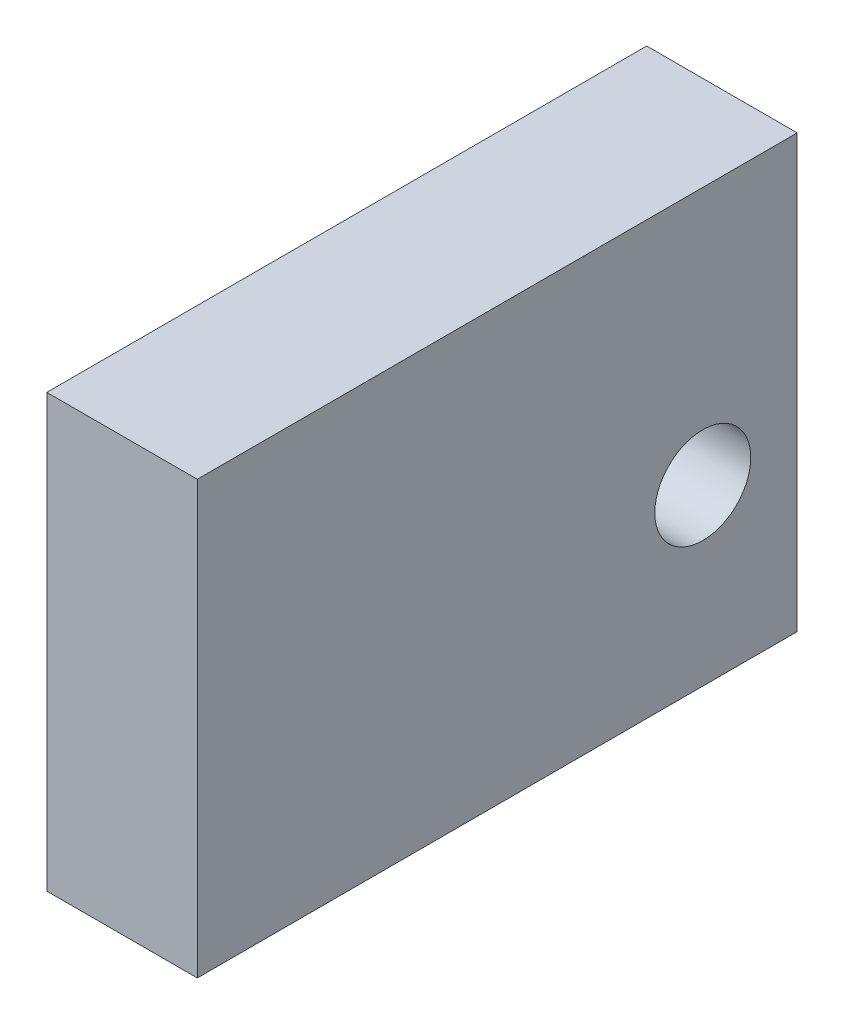
SolidWorks part; units mm, degrees
ref_plane "Front Plane" through (0, 0, 0) normal (0, 0, 1) x (1, 0, 0)
ref_plane "Top Plane" through (0, 0, 0) normal (0, 1, 0) x (1, 0, 0)
ref_plane "Right Plane" through (0, 0, 0) normal (1, 0, 0) x (0, 0, -1)
sketch "Sketch1" plane through (0, 0, 0) normal (0, 1, 0) x (1, 0, 0)
  line L1 (-1.381, 31.8279) -> (14.548, 31.8279)
  line L2 (-1.381, 31.8279) -> (-1.381, -31.6721)
  line L3 (-1.381, -31.6721) -> (14.548, -31.6721)
  line L4 (14.548, 31.8279) -> (14.548, -31.6721)
  line L5 (-1.381, 31.8279) -> (14.548, -31.6721) construction
  line L6 (-1.381, -31.6721) -> (14.548, 31.8279) construction
  point P4 (6.5835, 0.0779)
  dimension "D1" = 63.5
  dimension "D2" = 15.929
extrude "Boss-Extrude1" add sketch "Sketch1" along normal blind 45.72
sketch "Sketch2" plane through (-1.381, 0, 0) normal (-1, 0, 0) x (0, 0, 1)
  line L0 (-32.1974, 18.4248) -> (-21.8344, 18.4248) construction
  line L2 (-21.8344, 18.4248) -> (-21.8344, 0) construction
  line L3 (-31.8279, 0) -> (31.6721, 0) construction
  circle A0 centre (-21.8344, 18.4248) radius 5.08
  point P5 (-21.3688, 29.7859)
  point P6 (-21.8344, 18.4248)
  point P8 (0, 0)
  dimension "D3" = 10.16
  dimension "D2" = 10.363
extrude "Cut-Extrude1" cut sketch "Sketch2" against normal blind 50.8
